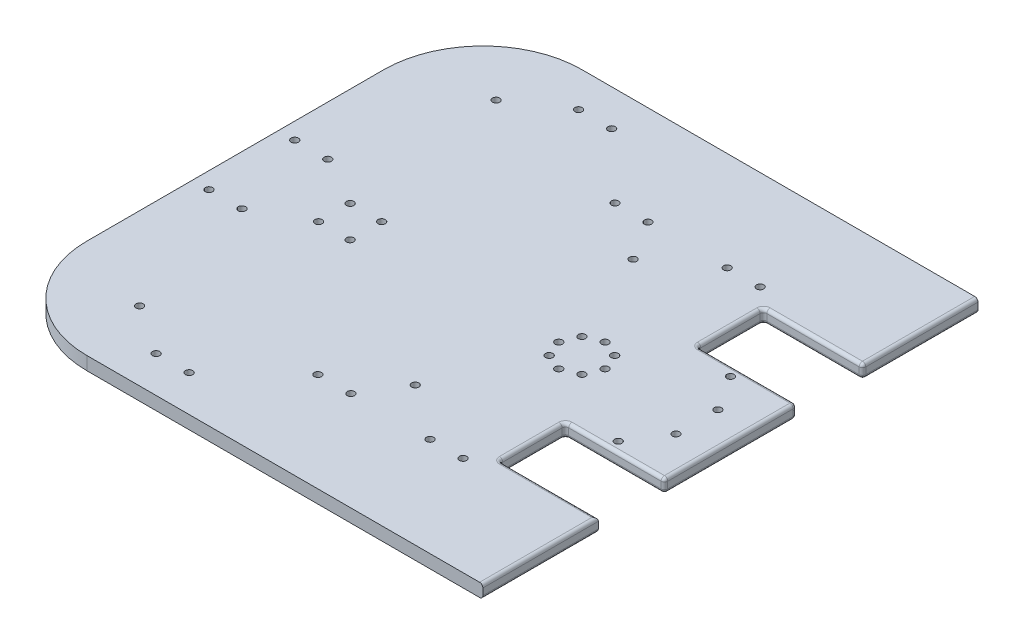
SolidWorks part; units mm, degrees
ref_plane "前视基准面" through (0, 0, 0) normal (0, 0, 1) x (1, 0, 0)
ref_plane "上视基准面" through (0, 0, 0) normal (0, 1, 0) x (1, 0, 0)
ref_plane "右视基准面" through (0, 0, 0) normal (1, 0, 0) x (0, 0, -1)
other "Configuration Table"
sketch "草图1" plane through (0, 0, 0) normal (0, 1, 0) x (1, 0, 0)
  line L1 (-150, 75) -> (150, 75)
  line L2 (-150, 75) -> (-150, -75)
  line L3 (-150, -75) -> (150, -75)
  line L4 (150, 75) -> (150, -75)
  dimension "D1" = 150
  dimension "D2" = 150
  dimension "D3" = 300
  dimension "D4" = 75
extrude "凸台-拉伸1" add sketch "草图1" along normal blind 4
fillet "圆角4" radius 30 1 edges at (-150, 2, 75) type face fillet first side face at (-150, 2, 0) second side face at (0, 2, 75)
fillet "圆角5" radius 30 1 edges at (-150, 2, -75) type face fillet first side face at (-150, 2, -15) second side face at (0, 2, -75)
fillet "圆角6" radius 30 1 edges at (150, 2, -75) type face fillet first side face at (15, 2, -75) second side face at (150, 2, 0)
fillet "圆角7" radius 30 1 edges at (150, 2, 75) type face fillet first side face at (150, 2, 15) second side face at (15, 2, 75)
sketch "草图2" plane through (0, 0, 0) normal (0, -1, 0) x (1, 0, 0)
  line L0 (0, 0) -> (-45, 0)
  line L1 (2.2, 0) -> (-2.2, 0) construction
  line L3 (0, -2.2) -> (0, 2.2) construction
  point P5 (-45, 7.02)
  dimension "D1" = 45
  dimension "D2" = 45
  dimension "D3" = 7.02
hole_wizard "Ø2.2 (2.2) 直径孔1" positions "草图3" profile "草图4" hole size "Ø2.2" standard "ANSI Metric" end condition up to next
sketch "草图3" plane through (0, 0, 0) normal (0, -1, 0) x (-1, 0, 0)
  point P0 (45, -7.02)
sketch "草图4" plane through (-45, 0, 7.02) normal (1, 0, 0) x (0, 0, -1)
  line L0 (0, 0) -> (0, 4)
  line L1 (0, 4) -> (1.1, 4)
  line L2 (1.1, 4) -> (1.1, 0)
  line L5 (1.1, 0) -> (0, 0)
  line L11 (0, -6.35) -> (0, 107.95) construction
  dimension "通孔孔直径" = 2.2
  dimension "通孔孔深度" = 4
ref_axis "基准轴1" through (-45, 0, 0) along (0, -1, 0)
pattern_circular "阵列(圆周)1" count 8 over 360 about axis through (-45, 0, 0) along (0, -1, 0) of "Ø2.2 (2.2) 直径孔1" reverse direction yes
mirror "镜向1" about plane through (0, 0, 0) normal (1, 0, 0) of "阵列(圆周)1", "Ø2.2 (2.2) 直径孔1"
sketch "草图5" plane through (0, 0, 0) normal (0, -1, 0) x (1, 0, 0)
  line L0 (-150, -45) -> (-150, 45) construction
  line L1 (2.2, 0) -> (-2.2, 0) construction
  point P0 (-120, 4.775)
  point P1 (-120, -4.78)
  point P6 (-110.45, -4.78)
  point P7 (-110.45, 4.775)
  dimension "D1" = 30
  dimension "D2" = 4.775
  dimension "D3" = 4.78
  dimension "D4" = 30
  dimension "D5" = 9.55
  dimension "D6" = 4.78
  dimension "D7" = 4.775
  dimension "D8" = 9.55
hole_wizard "Ø2.2 (2.2) 直径孔2" positions "草图6" profile "草图7" hole size "Ø2.2" standard "ANSI Metric" end condition up to next
sketch "草图6" plane through (0, 0, 0) normal (0, -1, 0) x (-1, 0, 0)
  point P0 (120, 4.78)
  point P3 (120, -4.775)
  point P6 (110.45, -4.775)
  point P9 (110.45, 4.78)
sketch "草图7" plane through (-120, 0, -4.78) normal (1, 0, 0) x (0, 0, -1)
  line L0 (0, 0) -> (0, 4)
  line L1 (0, 4) -> (1.1, 4)
  line L2 (1.1, 4) -> (1.1, 0)
  line L5 (1.1, 0) -> (0, 0)
  line L11 (0, -6.35) -> (0, 107.95) construction
  dimension "通孔孔直径" = 2.2
  dimension "通孔孔深度" = 4
mirror "镜向2" about plane through (0, 0, 0) normal (1, 0, 0) of "Ø2.2 (2.2) 直径孔2"
sketch "草图8" plane through (0, 4, 0) normal (0, 1, 0) x (1, 0, 0)
  line L0 (0, -2.2) -> (0, 2.2) construction
  line L1 (0, 0) -> (-45, 0) construction
  line L2 (-2.2, 0) -> (2.2, 0) construction
  point P0 (-30, 18)
  point P1 (-40, 18)
  point P2 (-40, -18)
  point P3 (-30, -18)
  dimension "D1" = 30
  dimension "D2" = 18
  dimension "D3" = 40
  dimension "D4" = 18
  dimension "D5" = 18
  dimension "D6" = 40
  dimension "D7" = 30
  dimension "D8" = 18
hole_wizard "Ø2.2 (2.2) 直径孔4" positions "草图13" profile "草图14" hole size "Ø2.2" standard "ANSI Metric" end condition up to next
sketch "草图13" plane through (0, 4, 0) normal (0, 1, 0) x (1, 0, 0)
  line L0 (-120, -75) -> (120, -75) construction
  line L1 (0, -2.2) -> (0, 2.2) construction
  point P0 (100, -64)
  point P2 (110, -64)
  point P4 (-100, -64)
  point P6 (-110, -64)
  dimension "D1" = 11
  dimension "D2" = 11
  dimension "D3" = 11
  dimension "D4" = 11
  dimension "D5" = 110
  dimension "D6" = 100
  dimension "D7" = 110
  dimension "D8" = 100
sketch "草图14" plane through (100, 4, 64) normal (1, 0, 0) x (0, 0, 1)
  line L0 (0, 0) -> (0, 4)
  line L1 (0, 4) -> (1.1, 4)
  line L2 (1.1, 4) -> (1.1, 0)
  line L5 (1.1, 0) -> (0, 0)
  line L11 (0, -6.35) -> (0, 107.95) construction
  dimension "通孔孔直径" = 2.2
  dimension "通孔孔深度" = 4
mirror "镜向4" about plane through (0, 0, 0) normal (0, 0, 1) of "Ø2.2 (2.2) 直径孔4"
hole_wizard "Ø2.2 (2.2) Diameter Hole1" positions "草图15" profile "草图16" hole size "Ø2.2" standard "ANSI Metric" end condition up to next
sketch "草图15" plane through (0, 4, 0) normal (0, 1, 0) x (1, 0, 0)
  line L0 (0, -2.2) -> (0, 2.2) construction
  line L1 (-2.2, 0) -> (2.2, 0) construction
  point P0 (-125, 54)
  dimension "D1" = 125
  dimension "D2" = 54
sketch "草图16" plane through (-125, 4, -54) normal (1, 0, 0) x (0, 0, 1)
  line L0 (0, 0) -> (0, 4)
  line L1 (0, 4) -> (1.1, 4)
  line L2 (1.1, 4) -> (1.1, 0)
  line L5 (1.1, 0) -> (0, 0)
  line L11 (0, -6.35) -> (0, 107.95) construction
  dimension "通孔孔直径" = 2.2
  dimension "通孔孔深度" = 4
mirror "镜向5" about plane through (0, 0, 0) normal (1, 0, 0) of "Ø2.2 (2.2) Diameter Hole1" second plane through (0, 0, 0) second plane normal (0, 0, 1)
hole_wizard "Ø2.2 (2.2) 直径孔6" positions "草图17" profile "草图18" hole size "Ø2.2" standard "ANSI Metric" end condition up to next
sketch "草图17" plane through (0, 4, 0) normal (0, 1, 0) x (1, 0, 0)
  line L0 (0, -2.2) -> (0, 2.2) construction
  line L1 (-2.2, 0) -> (2.2, 0) construction
  point P0 (-62.5, 33)
  point P13 (-62.5, -33)
  point P14 (62.5, -33)
  point P15 (62.5, 33)
  dimension "D1" = 62.5
  dimension "D2" = 33
sketch "草图18" plane through (-62.5, 4, -33) normal (1, 0, 0) x (0, 0, 1)
  line L0 (0, 0) -> (0, 4)
  line L1 (0, 4) -> (1.1, 4)
  line L2 (1.1, 4) -> (1.1, 0)
  line L5 (1.1, 0) -> (0, 0)
  line L11 (0, -6.35) -> (0, 107.95) construction
  dimension "通孔孔直径" = 2.2
  dimension "通孔孔深度" = 4
sketch "草图19" plane through (0, 4, 0) normal (0, 1, 0) x (1, 0, 0)
  line L0 (-150, 45) -> (-150, -45) construction
  point P0 (-145, 13)
  point P2 (-135, 13)
  dimension "D1" = 5
  dimension "D2" = 10
  dimension "D3" = 13
  dimension "D4" = 13
hole_wizard "Ø2.2 (2.2) Diameter Hole2" positions "草图19" profile "草图20" hole size "Ø2.2" standard "ANSI Metric" end condition up to next
sketch "草图20" plane through (-145, 4, -13) normal (1, 0, 0) x (0, 0, 1)
  line L0 (0, 0) -> (0, 4)
  line L1 (0, 4) -> (1.1, 4)
  line L2 (1.1, 4) -> (1.1, 0)
  line L5 (1.1, 0) -> (0, 0)
  line L11 (0, -6.35) -> (0, 107.95) construction
  dimension "Thru Hole Dia." = 2.2
  dimension "Thru Hole Depth" = 4
mirror "镜向6" about plane through (0, 0, 0) normal (1, 0, 0) of "Ø2.2 (2.2) Diameter Hole2" second plane through (0, 0, 0) second plane normal (0, 0, 1)
sketch "草图21" plane through (0, 4, 0) normal (0, 1, 0) x (1, 0, 0)
  line L0 (-2.2, 0) -> (2.2, 0) construction
  line L1 (-150, 45) -> (-150, -45) construction
  line L2 (150, -45) -> (150, 45) construction
  point P0 (-80, 45)
  point P2 (-70, 45)
  point P4 (-46, 45)
  point P6 (-36, 45)
  point P8 (4, 45)
  point P10 (14, 45)
  point P23 (62, 45)
  point P25 (72, 45)
  dimension "D1" = 45
  dimension "D2" = 45
  dimension "D3" = 45
  dimension "D4" = 45
  dimension "D5" = 10
  dimension "D6" = 10
  dimension "D7" = 70
  dimension "D8" = 34
  dimension "D9" = 45
  dimension "D10" = 45
  dimension "D11" = 10
  dimension "D12" = 45
  dimension "D13" = 45
  dimension "D14" = 58
  dimension "D15" = 78
  dimension "D16" = 10
hole_wizard "Ø2.2 (2.2) Diameter Hole3" positions "草图21" profile "草图22" hole size "Ø2.2" standard "ANSI Metric" end condition up to next
sketch "草图22" plane through (-80, 4, -45) normal (1, 0, 0) x (0, 0, 1)
  line L0 (0, 0) -> (0, 4)
  line L1 (0, 4) -> (1.1, 4)
  line L2 (1.1, 4) -> (1.1, 0)
  line L5 (1.1, 0) -> (0, 0)
  line L11 (0, -6.35) -> (0, 107.95) construction
  dimension "Thru Hole Dia." = 2.2
  dimension "Thru Hole Depth" = 4
mirror "镜向7" about plane through (0, 0, 0) normal (0, 0, 1) of "Ø2.2 (2.2) Diameter Hole3"
sketch "草图23" plane through (0, 0, 0) normal (0, -1, 0) x (1, 0, 0)
  line L0 (0, -2.2) -> (0, 2.2) construction
  line L1 (2.2, 0) -> (-2.2, 0) construction
  point P0 (-10.16, 6.35)
  dimension "D1" = 10.16
  dimension "D2" = 6.35
hole_wizard "Ø2.2 (2.2) Diameter Hole4" positions "草图23" profile "草图24" hole size "Ø2.2" standard "ANSI Metric" end condition up to next
sketch "草图24" plane through (-10.16, 0, 6.35) normal (1, 0, 0) x (0, 0, -1)
  line L0 (0, 0) -> (0, 4)
  line L1 (0, 4) -> (1.1, 4)
  line L2 (1.1, 4) -> (1.1, 0)
  line L5 (1.1, 0) -> (0, 0)
  line L11 (0, -6.35) -> (0, 107.95) construction
  dimension "Thru Hole Dia." = 2.2
  dimension "Thru Hole Depth" = 4
mirror "镜向8" about plane through (0, 0, 0) normal (0, 0, 1) of "Ø2.2 (2.2) Diameter Hole4" second plane through (0, 0, 0) second plane normal (1, 0, 0)
sketch "草图25" plane through (0, 0, 0) normal (0, 0, 1) x (1, 0, 0)
  line L0 (-120, 4) -> (120, 4) construction
  line L1 (0, 4) -> (150, 4)
  line L2 (0, 4) -> (0, 0)
  line L3 (0, 0) -> (150, 0)
  line L4 (150, 4) -> (150, 0)
sketch "草图26" plane through (0, 4, 0) normal (0, 1, 0) x (1, 0, 0)
  line L0 (-2.2, 0) -> (2.2, 0) construction
  line L1 (0, -2.2) -> (0, 2.2) construction
  point P0 (-17, 17)
  dimension "D1" = 17
  dimension "D2" = 17
hole_wizard "Ø2.2 (2.2) Diameter Hole5" positions "草图26" profile "草图27" hole size "Ø2.2" standard "ANSI Metric" end condition up to next
sketch "草图27" plane through (-17, 4, -17) normal (1, 0, 0) x (0, 0, 1)
  line L0 (0, 0) -> (0, 4)
  line L1 (0, 4) -> (1.1, 4)
  line L2 (1.1, 4) -> (1.1, 0)
  line L5 (1.1, 0) -> (0, 0)
  line L11 (0, -6.35) -> (0, 107.95) construction
  dimension "Thru Hole Dia." = 2.2
  dimension "Thru Hole Depth" = 4
mirror "镜向9" about plane through (0, 0, 0) normal (0, 0, 1) of "Ø2.2 (2.2) Diameter Hole5" second plane through (0, 0, 0) second plane normal (1, 0, 0)
extrude "切除-拉伸2" cut sketch "草图25" against normal through all both and the other way through all
sketch "草图29" plane through (0, 4, 0) normal (0, 1, 0) x (1, 0, 0)
  line L0 (0, -2.2) -> (0, 2.2) construction
  line L1 (-30, 20) -> (0, 20)
  line L2 (-30, 20) -> (-30, 40)
  line L3 (-30, 40) -> (0, 40)
  line L4 (0, 20) -> (0, 40)
  line L5 (0, 75) -> (-120, 75) construction
  dimension "D1" = 35
  dimension "D2" = 30
  dimension "D3" = 20
extrude "切除-拉伸3" cut sketch "草图29" against normal through all
mirror "镜向10" about plane through (0, 0, 0) normal (0, 0, 1) of "切除-拉伸3"
fillet "圆角8" radius 1 25 edges at (0, 4, 57.5) (0, 0, 57.5) (-15, 0, 20) (-15, 4, 20) (-30, 2, 20) (-15, 0, 40) (-15, 4, 40) (-30, 2, 40) (-30, 0, 30) (-30, 4, 30) (0, 2, 20) (0, 4, 0) (0, 0, 0) (-30, 2, -20) (-15, 0, -20) (0, 2, -20) (-15, 4, -20) (-30, 4, -30) (-30, 2, -40) (-30, 0, -30) (0, 4, -57.5) (0, 0, -57.5) (0, 2, -40) (-15, 0, -40) (-15, 4, -40)
